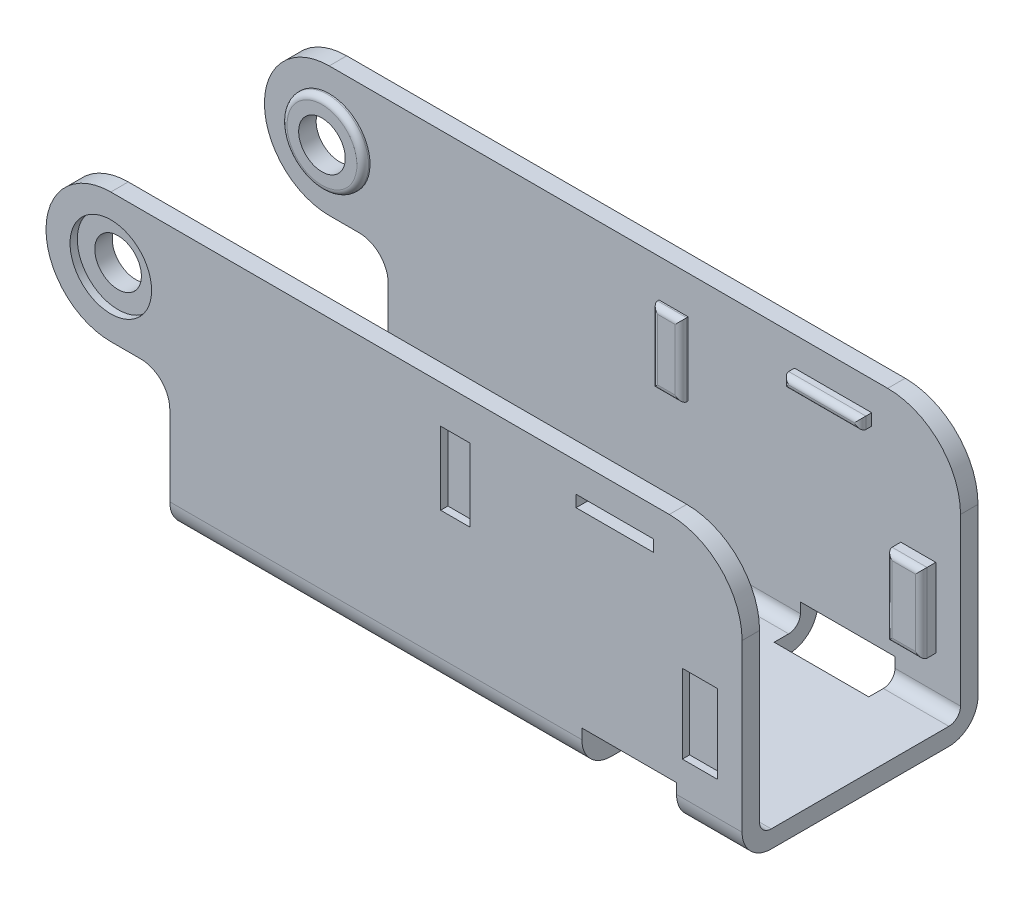
SolidWorks part; units mm, degrees
material "Chrome Stainless Steel"
ref_plane "Front Plane" through (0, 0, 0) normal (0, 0, 1) x (1, 0, 0)
ref_plane "Top Plane" through (0, 0, 0) normal (0, 1, 0) x (1, 0, 0)
ref_plane "Right Plane" through (0, 0, 0) normal (1, 0, 0) x (0, 0, -1)
ref_axis "X-axis" through (-88.99, 0, 0) along (1, 0, 0)
ref_axis "Y-axis" through (0, -55, 0) along (0, 1, 0)
ref_axis "Z-axis" through (0, 0, 55) along (0, 0, -1)
sketch "Sketch1" plane through (0, 0, 0) normal (0, 0, 1) x (1, 0, 0)
  line L0 (0, 0) -> (49.911, 0)
  line L1 (49.911, 0) -> (49.911, 23.368)
  line L2 (49.911, 23.368) -> (-5.1435, 23.368)
  line L3 (-5.1435, 12.065) -> (0, 12.065)
  line L4 (0, 12.065) -> (0, 0)
  arc A0 (-5.1435, 23.368) -> (-5.1435, 12.065) centre (-5.1435, 17.7165) ccw
  point P9 (-10.795, 17.7165)
  dimension "D1" = 49.911
  dimension "D2" = 11.303
  dimension "D3" = 23.368
  dimension "D4" = 60.706
extrude "Boss-Extrude1" add sketch "Sketch1" along normal mid plane 20.574
sketch "Sketch2" plane through (0, 0, 10.287) normal (0, 0, 1) x (1, 0, 0)
  circle A0 centre (-5.1435, 17.7165) radius 3.556
  dimension "D1" = 7.112
extrude "Cut-Extrude1" cut sketch "Sketch2" against normal blind 0.635
mirror "Mirror1" about plane through (0, 0, 0) normal (0, 0, 1) of "Cut-Extrude1"
sketch "Sketch3" plane through (0, 0, 10.287) normal (0, 0, 1) x (1, 0, 0)
  line L0 (49.911, 0) -> (49.911, 23.368) construction
  line L1 (47.752, 5.461) -> (44.704, 5.461)
  line L2 (47.752, 5.461) -> (47.752, 12.319)
  line L3 (47.752, 12.319) -> (44.704, 12.319)
  line L4 (44.704, 5.461) -> (44.704, 12.319)
  line L5 (49.911, 23.368) -> (-5.1435, 23.368) construction
  dimension "D1" = 2.159
  dimension "D2" = 6.858
  dimension "D3" = 3.048
  dimension "D4" = 11.049
extrude "Cut-Extrude2" cut sketch "Sketch3" against normal blind 0.635
sketch "Sketch4" plane through (0, 0, 10.287) normal (0, 0, 1) x (1, 0, 0)
  line L0 (49.911, 23.368) -> (-5.1435, 23.368) construction
  line L1 (42.164, 19.812) -> (35.433, 19.812)
  line L2 (42.164, 19.812) -> (42.164, 20.828)
  line L3 (42.164, 20.828) -> (35.433, 20.828)
  line L4 (35.433, 19.812) -> (35.433, 20.828)
  line L5 (49.911, 0) -> (49.911, 23.368) construction
  dimension "D1" = 2.54
  dimension "D2" = 7.747
  dimension "D3" = 6.731
  dimension "D4" = 1.016
extrude "Cut-Extrude3" cut sketch "Sketch4" against normal blind 1.016
sketch "Sketch5" plane through (0, 0, 10.287) normal (0, 0, 1) x (1, 0, 0)
  line L0 (49.911, 0) -> (49.911, 23.368) construction
  line L1 (23.622, 13.716) -> (26.162, 13.716)
  line L2 (23.622, 13.716) -> (23.622, 20.066)
  line L3 (23.622, 20.066) -> (26.162, 20.066)
  line L4 (26.162, 13.716) -> (26.162, 20.066)
  line L5 (49.911, 23.368) -> (-5.1435, 23.368) construction
  dimension "D1" = 2.54
  dimension "D2" = 6.35
  dimension "D3" = 23.749
  dimension "D4" = 3.302
extrude "Cut-Extrude4" cut sketch "Sketch5" against normal blind 0.635
mirror "Mirror2" about plane through (0, 0, 0) normal (0, 0, 1) of "Cut-Extrude3", "Cut-Extrude2", "Cut-Extrude4"
fillet "Fillet1" radius 6.35 1 edges at (49.911, 23.368, 0)
fillet "Fillet2" radius 2.54 3 edges at (24.9555, 0, 10.287) (0, 12.065, 0) (24.9555, 0, -10.287)
sketch "Sketch8" plane through (49.911, 0, 0) normal (1, 0, 0) x (0, 0, -1)
  line L0 (-8.763, 23.368) -> (-8.763, 2.54)
  line L1 (-10.287, 23.368) -> (10.287, 23.368) construction
  line L3 (8.763, 23.368) -> (8.763, 2.54)
  line L7 (-8.763, 23.368) -> (8.763, 23.368)
  line L8 (-7.747, 1.524) -> (7.747, 1.524)
  arc A20 (-8.763, 2.54) -> (-7.747, 1.524) centre (-7.747, 2.54) ccw
  arc A21 (-8.763, 2.54) -> (-7.747, 1.524) centre (-7.747, 2.54) ccw
  arc A23 (7.747, 1.524) -> (8.763, 2.54) centre (7.747, 2.54) ccw
  arc A24 (7.747, 1.524) -> (8.763, 2.54) centre (7.747, 2.54) ccw
  dimension "D3" = 1.524
  dimension "D4" = 1.524
extrude "Cut-Extrude5" cut sketch "Sketch8" against normal through all
sketch "Sketch9" plane through (0, 0, 8.763) normal (0, 0, -1) x (-1, 0, 0)
  line L0 (-23.622, 13.716) -> (-23.622, 20.066) construction
  line L1 (-23.622, 20.066) -> (-26.162, 20.066) construction
  line L2 (-26.162, 20.066) -> (-26.162, 13.716) construction
  line L3 (-26.162, 13.716) -> (-23.622, 13.716) construction
  line L4 (-42.164, 20.828) -> (-42.164, 19.812) construction
  line L5 (-42.164, 19.812) -> (-35.433, 19.812) construction
  line L6 (-35.433, 19.812) -> (-35.433, 20.828) construction
  line L7 (-35.433, 20.828) -> (-42.164, 20.828) construction
  line L8 (-47.752, 12.319) -> (-47.752, 5.461) construction
  line L9 (-47.752, 5.461) -> (-44.704, 5.461) construction
  line L10 (-44.704, 5.461) -> (-44.704, 12.319) construction
  line L11 (-44.704, 12.319) -> (-47.752, 12.319) construction
  line L12 (-23.622, 13.716) -> (-23.622, 20.066)
  line L13 (-23.622, 20.066) -> (-26.162, 20.066)
  line L14 (-26.162, 20.066) -> (-26.162, 13.716)
  line L15 (-26.162, 13.716) -> (-23.622, 13.716)
  line L16 (-42.164, 20.828) -> (-42.164, 19.812)
  line L17 (-42.164, 19.812) -> (-35.433, 19.812)
  line L18 (-35.433, 19.812) -> (-35.433, 20.828)
  line L19 (-35.433, 20.828) -> (-42.164, 20.828)
  line L20 (-47.752, 12.319) -> (-47.752, 5.461)
  line L21 (-47.752, 5.461) -> (-44.704, 5.461)
  line L22 (-44.704, 5.461) -> (-44.704, 12.319)
  line L23 (-44.704, 12.319) -> (-47.752, 12.319)
  circle A0 centre (5.1435, 17.7165) radius 3.556 construction
  circle A1 centre (5.1435, 17.7165) radius 3.556
extrude "Boss-Extrude2" add sketch "Sketch9" along normal blind 0.635 contours L14 L15 L12 L13 | A1 region at (24.892, 16.891, 8.763) region at (-5.1435, 17.7165, 8.763)
sketch "Sketch10" plane through (0, 0, 8.763) normal (0, 0, -1) x (-1, 0, 0)
  line L0 (-42.164, 20.828) -> (-42.164, 19.812) construction
  line L1 (-35.433, 19.812) -> (-35.433, 20.828) construction
  line L2 (-42.164, 19.812) -> (-35.433, 19.812) construction
  line L3 (-35.433, 20.828) -> (-42.164, 20.828) construction
  line L4 (-42.164, 20.828) -> (-42.164, 19.812)
  line L5 (-35.433, 19.812) -> (-35.433, 20.828)
  line L6 (-42.164, 19.812) -> (-35.433, 19.812)
  line L7 (-35.433, 20.828) -> (-42.164, 20.828)
extrude "Boss-Extrude3" add sketch "Sketch10" along normal blind 1.016
sketch "Sketch12" plane through (0, 0, 8.763) normal (0, 0, -1) x (-1, 0, 0)
  line L4 (-47.752, 12.319) -> (-47.752, 5.461)
  line L5 (-47.752, 5.461) -> (-44.704, 5.461)
  line L6 (-44.704, 5.461) -> (-44.704, 12.319)
  line L7 (-44.704, 12.319) -> (-47.752, 12.319)
  line L8 (-47.752, 12.319) -> (-47.752, 5.461)
  line L9 (-47.752, 5.461) -> (-44.704, 5.461)
  line L10 (-44.704, 5.461) -> (-44.704, 12.319)
  line L11 (-44.704, 12.319) -> (-47.752, 12.319)
  dimension "D1" = 0
extrude "Boss-Extrude4" add sketch "Sketch12" along normal blind 1.27
fillet "Fillet5" radius 0.508 13 edges at (24.892, 20.066, 8.128) (23.622, 16.891, 8.128) (24.892, 13.716, 8.128) (26.162, 16.891, 8.128) (35.433, 20.32, 7.747) (38.7985, 19.812, 7.747) (42.164, 20.32, 7.747) (38.7985, 20.828, 7.747) (-5.1435, 21.2725, 8.128) (44.704, 8.89, 7.493) (46.228, 5.461, 7.493) (47.752, 8.89, 7.493) (46.228, 12.319, 7.493)
mirror "Mirror4" about plane through (0, 0, 0) normal (0, 0, 1) of "Boss-Extrude4", "Boss-Extrude3", "Boss-Extrude2", "Fillet5"
hole_wizard "1 (0.16) Diameter Hole1" positions "Sketch6" profile "Sketch7" hole size "1" standard "ANSI Inch" end condition through all
sketch "Sketch6" plane through (0, 0, 9.652) normal (0, 0, 1) x (1, 0, 0)
  point P0 (-5.1435, 17.7165)
sketch "Sketch7" plane through (-5.1435, 17.7165, 9.652) normal (1, 0, 0) x (0, -1, 0)
  line L0 (0, 0) -> (0, 19.939)
  line L1 (0, 19.939) -> (2.032, 19.939)
  line L2 (2.032, 19.939) -> (2.032, 0)
  line L5 (2.032, 0) -> (0, 0)
  line L11 (0, -6.35) -> (0, 107.95) construction
  dimension "Thru Hole Dia." = 4.064
  dimension "Thru Hole Depth" = 19.939
sketch "Sketch15" plane through (0, 0, 0) normal (0, -1, 0) x (1, 0, 0)
  line L4 (0, 7.747) -> (0, -7.747) construction
  circle A0 centre (4.9911, 0) radius 1.651
  circle A1 centre (44.6786, 0) radius 1.651
  point P5 (0, 0)
  dimension "D1" = 3.302
  dimension "D3" = 39.6875
  dimension "D2" = 4.9911
extrude "Boss-Extrude5" add sketch "Sketch15" along normal blind 1.397
fillet "Fillet6" radius 1.397 2 edges at (4.9911, -1.397, -1.651) (44.6786, -1.397, -1.651)
sketch "Sketch16" plane through (0, 1.524, 0) normal (0, -1, 0) x (1, 0, 0)
  line L0 (0, 7.747) -> (0, -7.747) construction
  circle A0 centre (13.0556, 0) radius 2.8575
  circle A1 centre (36.6141, 0) radius 2.8575
  circle A2 centre (4.9911, 0) radius 1.651 construction
  circle A3 centre (44.6786, 0) radius 1.651 construction
  point P13 (0, 0)
  dimension "D1" = 8.0645
  dimension "D2" = 8.0645
  dimension "D3" = 5.715
extrude "Boss-Extrude6" add sketch "Sketch16" along normal blind 3.302
sketch "Sketch20" plane through (0, -1.778, 0) normal (0, -1, 0) x (1, 0, 0)
  circle A0 centre (13.0556, 0) radius 2.0701
  circle A1 centre (36.6141, 0) radius 2.0701
  circle A3 centre (13.0556, 0) radius 2.8575 construction
  dimension "D1" = 0.7874
extrude "Cut-Extrude6" cut sketch "Sketch20" against normal through all
sketch "Sketch21" plane through (0, 0, 10.287) normal (0, 0, 1) x (1, 0, 0)
  line L0 (43.0276, 0) -> (46.3296, 0) construction
  line L1 (44.196, 0) -> (35.941, 0)
  line L2 (44.196, 0) -> (44.196, 3.429)
  line L3 (44.196, 3.429) -> (35.941, 3.429)
  line L4 (35.941, 0) -> (35.941, 3.429)
  line L5 (49.911, 0) -> (49.911, 2.54) construction
  line L6 (43.561, 23.368) -> (-5.1435, 23.368) construction
  dimension "D1" = 5.715
  dimension "D2" = 8.255
  dimension "D3" = 19.939
extrude "Cut-Extrude7" cut sketch "Sketch21" against normal blind 3.81
mirror "Mirror5" about plane through (0, 0, 0) normal (0, 0, 1) of "Cut-Extrude7"
